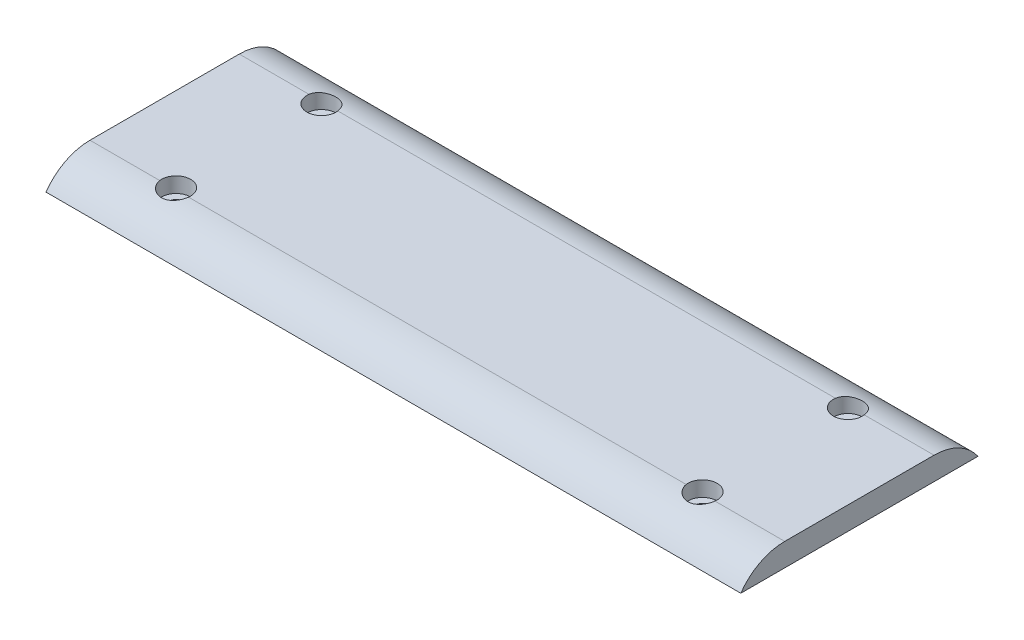
SolidWorks part; units mm, degrees
ref_plane "Front Plane" through (0, 0, 0) normal (0, 0, 1) x (1, 0, 0)
ref_plane "Top Plane" through (0, 0, 0) normal (0, 1, 0) x (1, 0, 0)
ref_plane "Right Plane" through (0, 0, 0) normal (1, 0, 0) x (0, 0, -1)
sketch "Sketch1" plane through (0, 0, 0) normal (0, 1, 0) x (1, 0, 0)
  line L0 (-45.4, 0) -> (45.4, 0) construction
  line L1 (-45.4, 15.5) -> (45.4, 15.5)
  line L2 (-45.4, 15.5) -> (-45.4, -15.5)
  line L3 (-45.4, -15.5) -> (45.4, -15.5)
  line L4 (45.4, 15.5) -> (45.4, -15.5)
  line L5 (0, 15.5) -> (0, -15.5) construction
  point P8 (0, 0)
  dimension "D1" = 90.8
  dimension "D2" = 31
extrude "Boss-Extrude1" add sketch "Sketch1" along normal blind 3
sketch "Sketch2" plane through (0, 3, 0) normal (0, 1, 0) x (1, 0, 0)
  line L0 (-34.4, 9.5) -> (-45.4, 9.5) construction
  line L1 (-45.4, 15.5) -> (-45.4, -15.5) construction
  line L2 (-34.4, -9.5) -> (-45.4, -9.5) construction
  line L3 (34.4, 9.5) -> (45.4, 9.5) construction
  line L4 (45.4, -15.5) -> (45.4, 15.5) construction
  line L5 (34.4, -9.5) -> (45.4, -9.5) construction
  line L6 (-34.4, 9.5) -> (-34.4, 15.5) construction
  line L7 (45.4, 15.5) -> (-45.4, 15.5) construction
  line L8 (34.4, 9.5) -> (34.4, 15.5) construction
  line L9 (34.4, -9.5) -> (34.4, -15.5) construction
  line L10 (-45.4, -15.5) -> (45.4, -15.5) construction
  line L11 (-34.4, -9.5) -> (-34.4, -15.5) construction
  circle A0 centre (-34.4, 9.5) radius 0.95
  circle A1 centre (34.4, 9.5) radius 0.95
  circle A2 centre (-34.4, -9.5) radius 0.95
  circle A3 centre (34.4, -9.5) radius 0.95
  dimension "D1" = 1.9
  dimension "D2" = 6
  dimension "D3" = 11
extrude "Cut-Extrude1" cut sketch "Sketch2" against normal blind 3
sketch "Sketch3" plane through (0, 3, 0) normal (0, 1, 0) x (1, 0, 0)
  circle A0 centre (-34.4, 9.5) radius 1.9
  circle A1 centre (-34.4, -9.5) radius 1.9
  circle A2 centre (34.4, 9.5) radius 1.9
  circle A3 centre (34.4, -9.5) radius 1.9
  dimension "D1" = 3.8
extrude "Cut-Extrude2" cut sketch "Sketch3" against normal blind 2
sketch "Sketch4" plane through (0, 0, 0) normal (0, -1, 0) x (1, 0, 0)
  line L0 (-27, 0) -> (27, 0) construction
  line L1 (-27, 3.5) -> (27, 3.5)
  line L2 (-27, 3.5) -> (-27, -3.5)
  line L3 (-27, -3.5) -> (27, -3.5)
  line L4 (27, 3.5) -> (27, -3.5)
  line L5 (0, 3.5) -> (0, -3.5) construction
  point P8 (0, 0)
  dimension "D1" = 54
  dimension "D2" = 7
extrude "Boss-Extrude2" add sketch "Sketch4" along normal blind 5
sketch "Sketch5" plane through (27, 0, 0) normal (1, 0, 0) x (0, 0, -1)
  line L0 (0, -5) -> (0, -6.1307) construction
  line L1 (3.5, -5) -> (-3.5, -5) construction
  circle A0 centre (0, -6.1307) radius 3.9
  dimension "D1" = 7.8
  dimension "D2" = 1.1307
extrude "Cut-Extrude3" cut sketch "Sketch5" against normal blind 54
fillet "Fillet1" radius 7 2 edges at (0, 3, 15.5) (0, 3, -15.5)
